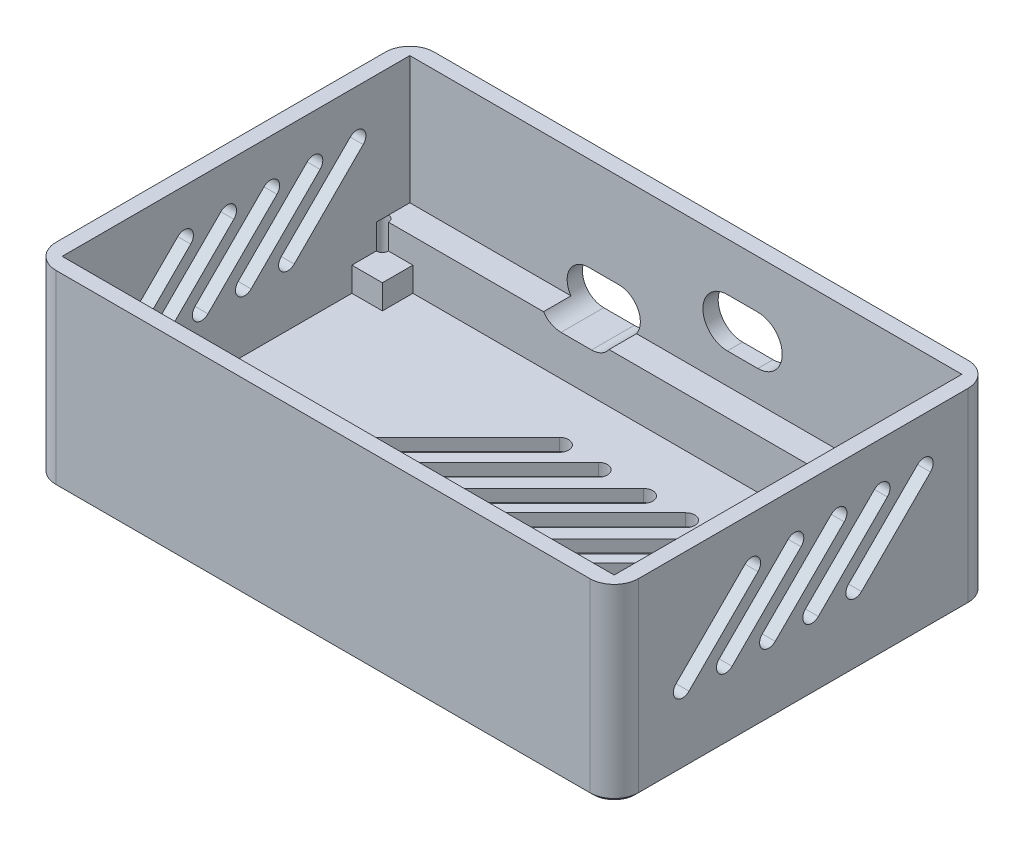
SolidWorks part; units mm, degrees
ref_plane "Front Plane" through (0, 0, 0) normal (0, 0, 1) x (1, 0, 0)
ref_plane "Top Plane" through (0, 0, 0) normal (0, 1, 0) x (1, 0, 0)
ref_plane "Right Plane" through (0, 0, 0) normal (1, 0, 0) x (0, 0, -1)
sketch "Croquis_contorno" plane through (0, 0, 0) normal (0, 1, 0) x (1, 0, 0)
  line L0 (-43.75, -28.75) -> (43.75, -28.75)
  line L1 (47.75, -24.75) -> (47.75, 29.25)
  line L2 (43.75, 33.25) -> (-43.75, 33.25)
  line L3 (-47.75, 29.25) -> (-47.75, -24.75)
  arc A0 (43.75, -28.75) -> (47.75, -24.75) centre (43.75, -24.75) ccw
  arc A1 (47.75, 29.25) -> (43.75, 33.25) centre (43.75, 29.25) ccw
  arc A2 (-43.75, 33.25) -> (-47.75, 29.25) centre (-43.75, 29.25) ccw
  arc A3 (-47.75, -24.75) -> (-43.75, -28.75) centre (-43.75, -24.75) ccw
  dimension "D3" = 4
  dimension "D1" = 95.5
  dimension "D2" = 62
extrude "Cuerpo" add sketch "Croquis_contorno" along normal blind 31
ref_plane "Plano_Top Plane_+31" through (0, 31, 0) normal (0, 1, 0) x (1, 0, 0)
sketch "Croquis_hueco_ESP32" plane through (0, 31, 0) normal (0, 1, 0) x (1, 0, 0)
  line L1 (-45.25, -26.25) -> (45.25, -26.25)
  line L2 (-45.25, -26.25) -> (-45.25, 30.75)
  line L3 (-45.25, 30.75) -> (45.25, 30.75)
  line L4 (45.25, -26.25) -> (45.25, 30.75)
  line L5 (-45.25, -26.25) -> (45.25, 30.75) construction
  line L6 (-45.25, 30.75) -> (45.25, -26.25) construction
  dimension "D1" = 90.5
  dimension "D2" = 57
extrude "Hueco_ESP32" cut sketch "Croquis_hueco_ESP32" against normal blind 20.9
ref_plane "Plano_Top Plane_+10_1" through (0, 10.1, 0) normal (0, 1, 0) x (1, 0, 0)
sketch "Croquis_hueco_PCB" plane through (0, 10.1, 0) normal (0, 1, 0) x (1, 0, 0)
  line L0 (45.25, -26.25) -> (45.25, 30.75) construction
  line L1 (-45.25, -26.25) -> (45.25, -26.25)
  line L2 (-45.25, -26.25) -> (-45.25, 26.25)
  line L3 (-45.25, 26.25) -> (45.25, 26.25)
  line L4 (45.25, -26.25) -> (45.25, 26.25)
  line L5 (-45.25, -26.25) -> (45.25, 26.25) construction
  line L6 (-45.25, 26.25) -> (45.25, -26.25) construction
  point P0 (0, 0)
  dimension "D1" = 90.5
  dimension "D2" = 52.5
extrude "Hueco_PCB" cut sketch "Croquis_hueco_PCB" against normal blind 8.1
ref_plane "Plano_Top Plane_+2" through (0, 2, 0) normal (0, 1, 0) x (1, 0, 0)
sketch "Croquis_apoyos" plane through (0, 2, 0) normal (0, 1, 0) x (1, 0, 0)
  line L0 (45.25, 26.25) -> (-45.25, 26.25) construction
  line L1 (-45.25, -26.25) -> (-40.25, -26.25)
  line L2 (-45.25, -26.25) -> (-45.25, -21.25)
  line L3 (-45.25, -21.25) -> (-40.25, -21.25)
  line L4 (-40.25, -26.25) -> (-40.25, -21.25)
  line L5 (-45.25, -26.25) -> (-40.25, -21.25) construction
  line L6 (-45.25, -21.25) -> (-40.25, -26.25) construction
  line L7 (-45.25, 21.25) -> (-40.25, 21.25)
  line L8 (-45.25, 21.25) -> (-45.25, 26.25)
  line L9 (-45.25, 26.25) -> (-40.25, 26.25)
  line L10 (-40.25, 21.25) -> (-40.25, 26.25)
  line L11 (-45.25, 21.25) -> (-40.25, 26.25) construction
  line L12 (-45.25, 26.25) -> (-40.25, 21.25) construction
  line L13 (45.25, -26.25) -> (45.25, 26.25) construction
  line L14 (40.25, -26.25) -> (45.25, -26.25)
  line L15 (40.25, -26.25) -> (40.25, -21.25)
  line L16 (40.25, -21.25) -> (45.25, -21.25)
  line L17 (45.25, -26.25) -> (45.25, -21.25)
  line L18 (40.25, -26.25) -> (45.25, -21.25) construction
  line L19 (40.25, -21.25) -> (45.25, -26.25) construction
  line L21 (40.25, 21.25) -> (45.25, 21.25)
  line L22 (40.25, 21.25) -> (40.25, 26.25)
  line L23 (40.25, 26.25) -> (45.25, 26.25)
  line L24 (45.25, 21.25) -> (45.25, 26.25)
  line L25 (40.25, 21.25) -> (45.25, 26.25) construction
  line L26 (40.25, 26.25) -> (45.25, 21.25) construction
  point P0 (-42.75, 23.75)
  point P11 (42.75, -23.75)
  point P18 (42.75, 23.75)
  dimension "D1" = 5
  dimension "D2" = 5
extrude "Apoyos_PCB" add sketch "Croquis_apoyos" along normal blind 4
sketch "Croquis_alivios" plane through (0, 2, 0) normal (0, 1, 0) x (1, 0, 0)
  circle A0 centre (-45.25, -26.25) radius 1
  circle A1 centre (-45.25, 26.25) radius 1
  circle A2 centre (45.25, -26.25) radius 1
  circle A3 centre (45.25, 26.25) radius 1
  dimension "D1" = 2
extrude "Alivios_esquinas" cut sketch "Croquis_alivios" along normal blind 8.1
sketch "Croquis_salidas" plane through (0, 0, 0) normal (0, 0, 1) x (1, 0, 0)
  line L0 (6.8, 19.1) -> (11.8, 19.1) construction
  line L1 (6.8, 23.1) -> (11.8, 23.1)
  line L2 (6.8, 15.1) -> (11.8, 15.1)
  line L3 (-15.96, 12.1) -> (-10.96, 12.1) construction
  line L4 (-15.96, 15.6) -> (-10.96, 15.6)
  line L5 (-15.96, 8.6) -> (-10.96, 8.6)
  arc A0 (6.8, 23.1) -> (6.8, 15.1) centre (6.8, 19.1) ccw
  arc A1 (11.8, 15.1) -> (11.8, 23.1) centre (11.8, 19.1) ccw
  arc A2 (-15.96, 15.6) -> (-15.96, 8.6) centre (-15.96, 12.1) ccw
  arc A3 (-10.96, 8.6) -> (-10.96, 15.6) centre (-10.96, 12.1) ccw
  point P2 (9.3, 19.1)
  point P7 (-13.46, 12.1)
  point P14 (0, 0)
extrude "Salidas_USB_y_panel" cut sketch "Croquis_salidas" against normal through all
sketch "Croquis_ventilas" plane through (0, 0, 0) normal (1, 0, 0) x (0, 0, -1)
  line L0 (-17.549, 11.9431) -> (-6.2353, 23.2569) construction
  line L1 (-18.6097, 13.0038) -> (-7.2959, 24.3175)
  line L2 (-16.4883, 10.8825) -> (-5.1746, 22.1962)
  line L3 (-10.4779, 11.9431) -> (0.8358, 23.2569) construction
  line L4 (-11.5386, 13.0038) -> (-0.2249, 24.3175)
  line L5 (-9.4173, 10.8825) -> (1.8964, 22.1962)
  line L6 (-3.4069, 11.9431) -> (7.9069, 23.2569) construction
  line L7 (-4.4675, 13.0038) -> (6.8462, 24.3175)
  line L8 (-2.3462, 10.8825) -> (8.9675, 22.1962)
  line L9 (3.6642, 11.9431) -> (14.9779, 23.2569) construction
  line L10 (2.6036, 13.0038) -> (13.9173, 24.3175)
  line L11 (4.7249, 10.8825) -> (16.0386, 22.1962)
  line L12 (10.7353, 11.9431) -> (22.049, 23.2569) construction
  line L13 (9.6746, 13.0038) -> (20.9883, 24.3175)
  line L14 (11.7959, 10.8825) -> (23.1097, 22.1962)
  arc A0 (-18.6097, 13.0038) -> (-16.4883, 10.8825) centre (-17.549, 11.9431) ccw
  arc A1 (-5.1746, 22.1962) -> (-7.2959, 24.3175) centre (-6.2353, 23.2569) ccw
  arc A2 (-11.5386, 13.0038) -> (-9.4173, 10.8825) centre (-10.4779, 11.9431) ccw
  arc A3 (1.8964, 22.1962) -> (-0.2249, 24.3175) centre (0.8358, 23.2569) ccw
  arc A4 (-4.4675, 13.0038) -> (-2.3462, 10.8825) centre (-3.4069, 11.9431) ccw
  arc A5 (8.9675, 22.1962) -> (6.8462, 24.3175) centre (7.9069, 23.2569) ccw
  arc A6 (2.6036, 13.0038) -> (4.7249, 10.8825) centre (3.6642, 11.9431) ccw
  arc A7 (16.0386, 22.1962) -> (13.9173, 24.3175) centre (14.9779, 23.2569) ccw
  arc A8 (9.6746, 13.0038) -> (11.7959, 10.8825) centre (10.7353, 11.9431) ccw
  arc A9 (23.1097, 22.1962) -> (20.9883, 24.3175) centre (22.049, 23.2569) ccw
  point P2 (-11.8921, 17.6)
  point P7 (-4.8211, 17.6)
  point P14 (2.25, 17.6)
  point P21 (9.3211, 17.6)
  point P28 (16.3921, 17.6)
  point P35 (0, 0)
extrude "Ventilas_laterales" cut sketch "Croquis_ventilas" along normal through all and the other way through all
sketch "Croquis_rejilla_piso" plane through (0, 0, 0) normal (0, 1, 0) x (1, 0, 0)
  line L0 (-35.7089, -12.2457) -> (-6.7175, 16.7457) construction
  line L1 (-36.7696, -11.185) -> (-7.7782, 17.8063)
  line L2 (-34.6482, -13.3063) -> (-5.6569, 15.685)
  line L3 (-28.6378, -12.2457) -> (0, 16.3921) construction
  line L4 (-29.6985, -11.185) -> (-1.0607, 17.4528)
  line L5 (-27.5772, -13.3063) -> (1.0607, 15.3315)
  line L6 (-21.2132, -12.2457) -> (7.4246, 16.3921) construction
  line L7 (-22.2739, -11.185) -> (6.364, 17.4528)
  line L8 (-20.1525, -13.3063) -> (8.4853, 15.3315)
  line L9 (-14.3189, -12.2457) -> (14.3189, 16.3921) construction
  line L10 (-15.3796, -11.185) -> (13.2583, 17.4528)
  line L11 (-13.2583, -13.3063) -> (15.3796, 15.3315)
  line L12 (-6.8943, -12.2457) -> (21.7435, 16.3921) construction
  line L13 (-7.955, -11.185) -> (20.6829, 17.4528)
  line L14 (-5.8336, -13.3063) -> (22.8042, 15.3315)
  line L15 (0, -12.2457) -> (28.6378, 16.3921) construction
  line L16 (-1.0607, -11.185) -> (27.5772, 17.4528)
  line L17 (1.0607, -13.3063) -> (29.6985, 15.3315)
  line L18 (6.364, -12.2457) -> (35.5321, 16.9225) construction
  line L19 (5.3033, -11.185) -> (34.4715, 17.9831)
  line L20 (7.4246, -13.3063) -> (36.5928, 15.8618)
  arc A0 (-36.7696, -11.185) -> (-34.6482, -13.3063) centre (-35.7089, -12.2457) ccw
  arc A1 (-5.6569, 15.685) -> (-7.7782, 17.8063) centre (-6.7175, 16.7457) ccw
  arc A2 (-29.6985, -11.185) -> (-27.5772, -13.3063) centre (-28.6378, -12.2457) ccw
  arc A3 (1.0607, 15.3315) -> (-1.0607, 17.4528) centre (0, 16.3921) ccw
  arc A4 (-22.2739, -11.185) -> (-20.1525, -13.3063) centre (-21.2132, -12.2457) ccw
  arc A5 (8.4853, 15.3315) -> (6.364, 17.4528) centre (7.4246, 16.3921) ccw
  arc A6 (-15.3796, -11.185) -> (-13.2583, -13.3063) centre (-14.3189, -12.2457) ccw
  arc A7 (15.3796, 15.3315) -> (13.2583, 17.4528) centre (14.3189, 16.3921) ccw
  arc A8 (-7.955, -11.185) -> (-5.8336, -13.3063) centre (-6.8943, -12.2457) ccw
  arc A9 (22.8042, 15.3315) -> (20.6829, 17.4528) centre (21.7435, 16.3921) ccw
  arc A10 (-1.0607, -11.185) -> (1.0607, -13.3063) centre (0, -12.2457) ccw
  arc A11 (29.6985, 15.3315) -> (27.5772, 17.4528) centre (28.6378, 16.3921) ccw
  arc A12 (5.3033, -11.185) -> (7.4246, -13.3063) centre (6.364, -12.2457) ccw
  arc A13 (36.5928, 15.8618) -> (34.4715, 17.9831) centre (35.5321, 16.9225) ccw
  point P2 (-21.2132, 2.25)
  point P7 (-14.3189, 2.0732)
  point P14 (-6.8943, 2.0732)
  point P21 (0, 2.0732)
  point P28 (7.4246, 2.0732)
  point P35 (14.3189, 2.0732)
  point P42 (20.948, 2.3384)
  point P49 (0, 0)
extrude "Rejilla_piso" cut sketch "Croquis_rejilla_piso" along normal blind 2
chamfer "Chaflan_base" distance 0.6 angle 45 8 edges at (0, 0, 28.75) (46.5784, 0, 27.5784) (47.75, 0, -2.25) (46.5784, 0, -32.0784) (0, 0, -33.25) (-46.5784, 0, -32.0784) (-47.75, 0, -2.25) (-46.5784, 0, 27.5784) tangent propagation no
